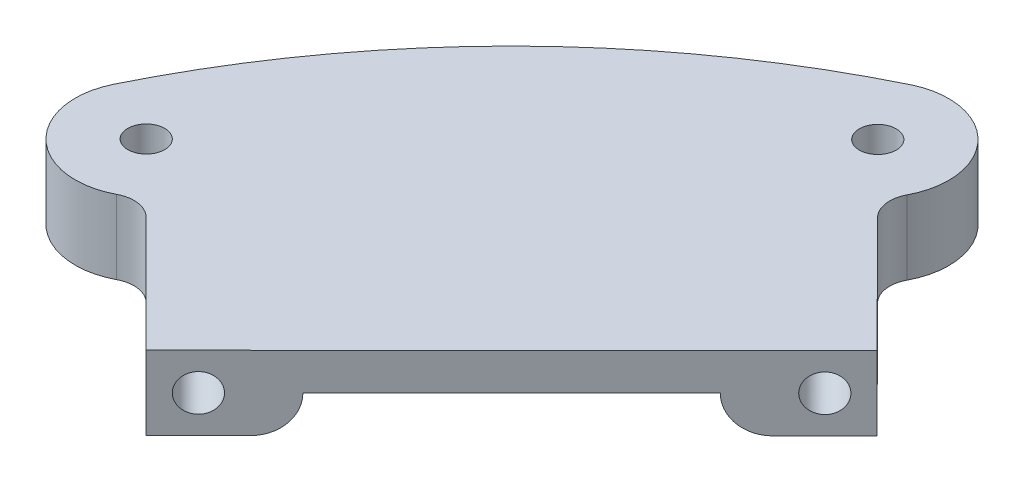
SolidWorks part; units mm, degrees
material "6061-T6 (SS)"
ref_plane "Front Plane" through (0, 0, 0) normal (0, 0, 1) x (1, 0, 0)
ref_plane "Top Plane" through (0, 0, 0) normal (0, 1, 0) x (1, 0, 0)
ref_plane "Right Plane" through (0, 0, 0) normal (1, 0, 0) x (0, 0, -1)
sketch "Sketch10" plane through (0, 0, 0) normal (0, 1, 0) x (1, 0, 0)
  line L9 (-7.544, -5.9741) -> (-70.4198, -68.719)
  line L10 (-38.9819, -37.3465) -> (-84.235, 8.0011) construction
  line L11 (-90.1755, -48.9543) -> (-70.4198, -68.719)
  line L12 (-27.2674, 13.8228) -> (-7.544, -5.9741)
  circle A0 centre (-101.8436, -37.281) radius 3.175
  arc A3 (-84.235, 8.0011) -> (-112.8542, -32.0525) centre (21.2082, -97.5917) ccw
  arc A10 (-112.8542, -32.0525) -> (-96.1439, -48.0552) centre (-101.8436, -37.281) ccw
  arc A11 (-96.1439, -48.0552) -> (-90.1755, -48.9543) centre (-93.7684, -52.5456) cw
  arc A12 (-28.154, 19.7931) -> (-27.2674, 13.8228) centre (-23.6686, 17.4083) ccw
  arc A13 (-44.1219, 36.5367) -> (-28.154, 19.7931) centre (-38.9163, 25.5152) cw
  arc A14 (-84.235, 8.0011) -> (-44.1219, 36.5367) centre (21.1377, -97.662) cw
  circle A15 centre (-38.9163, 25.5152) radius 3.175
  point P6 (-93.201, -45.9275)
  point P7 (0, 0)
  point P8 (0, 0)
  point P21 (-30.2878, 16.8546)
  dimension "D2" = 6.35
  dimension "D3" = 149.225
  dimension "D5" = 5.08
  dimension "D6" = 12.1889
  dimension "D10" = 44.45
  dimension "D4" = 44.45
  dimension "D7" = 27.9452
  dimension "D8" = 44.4136
  dimension "D9" = 85.1605
extrude "Boss-Extrude1" add sketch "Sketch10" along normal blind 12.7
sketch "Sketch13" plane through (-0.7771, 0, -0.7787) normal (0.7064, 0, 0.7078) x (0.7078, 0, -0.7064)
  line L0 (-98.3871, 12.7) -> (-9.5598, 12.7) construction
  line L1 (-85.6871, 12.7) -> (-98.3871, 12.7)
  line L2 (-85.6871, 12.7) -> (-85.6871, 0)
  line L3 (-85.6871, 0) -> (-98.3871, 0)
  line L4 (-98.3871, 12.7) -> (-98.3871, 0)
  line L5 (-98.3871, 12.7) -> (-85.6871, 0) construction
  line L6 (-53.9735, 12.7) -> (-53.9735, 0) construction
  line L7 (-98.3871, 0) -> (-9.5598, 0) construction
  circle A0 centre (-92.0371, 6.35) radius 3.175
  circle A1 centre (-15.9098, 6.35) radius 3.175
  dimension "D1" = 6.35
extrude "Tapped Hole for Lid" cut sketch "Sketch13" against normal blind 12.7 contours A0 L5 | L5 A0 | A1 region at (-65.925, 6.35, 64.2335)
sketch "Sketch14" plane through (-0.7771, 0, -0.7787) normal (0.7064, 0, 0.7078) x (0.7078, 0, -0.7064)
  line L0 (-9.5598, 12.7) -> (-9.5598, 0) construction
  line L1 (-85.6871, 0) -> (-98.3871, 0)
  line L2 (-85.6871, 0) -> (-85.6871, 12.7)
  line L3 (-85.6871, 12.7) -> (-98.3871, 12.7)
  line L4 (-98.3871, 0) -> (-98.3871, 12.7)
  line L5 (-85.6871, 0) -> (-98.3871, 12.7) construction
  line L6 (-85.6871, 12.7) -> (-98.3871, 0) construction
  line L7 (-22.2598, 12.7) -> (-9.5598, 12.7)
  line L8 (-22.2598, 12.7) -> (-22.2598, 0)
  line L9 (-22.2598, 0) -> (-9.5598, 0)
  line L10 (-9.5598, 12.7) -> (-9.5598, 0)
  line L11 (-22.2598, 12.7) -> (-9.5598, 0) construction
  line L12 (-22.2598, 0) -> (-9.5598, 12.7) construction
  line L13 (-92.0371, 6.35) -> (-15.9098, 6.35) construction
  line L14 (-79.3371, 6.35) -> (-28.6098, 6.35)
  line L15 (-85.6871, 0) -> (-22.2598, 0)
  arc A0 (-85.6871, 0) -> (-79.3371, 6.35) centre (-85.6871, 6.35) ccw
  arc A1 (-22.2598, 0) -> (-28.6098, 6.35) centre (-22.2598, 6.35) cw
  point P0 (-92.0371, 6.35)
  point P7 (-15.9098, 6.35)
  line M11 (-98.3871, 0) -> (-9.5598, 0)
extrude "Cut to Decrease Mass" cut sketch "Sketch14" against normal blind 50.8 contours A1 L14 A0 M11 region at (-38.9819, 3.0854, 37.3465)
fillet "Eigth Inch Internal Fillet" radius 3.175 3 edges at (-55.5954, 1.8599, -17.8418) (-94.1354, 1.8599, 20.6179) (-74.8654, 6.35, 1.3881)
equation "\"Pipe Diameter\"= 1in"
equation "\"Pipe Radial Distance\"= 3.01in"
equation "\"Rocket Diameter\"= 12in"
equation "\"Airframe Thickness\"= 0.125in"
equation "\"Arduino Mega Length\"= 101.52mm"
equation "\"Arduino Mega Width\"= 53.3mm"
equation "\"Interior Height\"= 2in"
equation "\"Wall Thickness\"= 0.5in"
equation "\"Assembly Hole Diameter\"= 0.25in"
equation "\"4-40 Standoff Depth\"= 0.1875in"
equation "\"Wire Hole Diameter\"= 0.1in"
equation "\"Flange Nut Height\"= 15 / 64in"
equation "\"Flange Nut Diameter\"= 19 / 32in"
equation "\"Assembly Bolt Length\"= 1in"
equation "\"D2@Sketch10\"=\"Assembly Hole Diameter\""
equation "\"D3@Sketch10\"=(\"Rocket Diameter\"/2)-\"Airframe Thickness\""
equation "\"D1@Boss-Extrude1\"=\"Wall Thickness\""
equation "\"D1@Sketch13\"=\"Assembly Hole Diameter\""
equation "\"D1@Tapped Hole for Lid\" = \"Assembly Bolt Length\" - \"Wall Thickness\""
equation "\"D1@Cut to Decrease Mass\" = \"Interior Height\""
